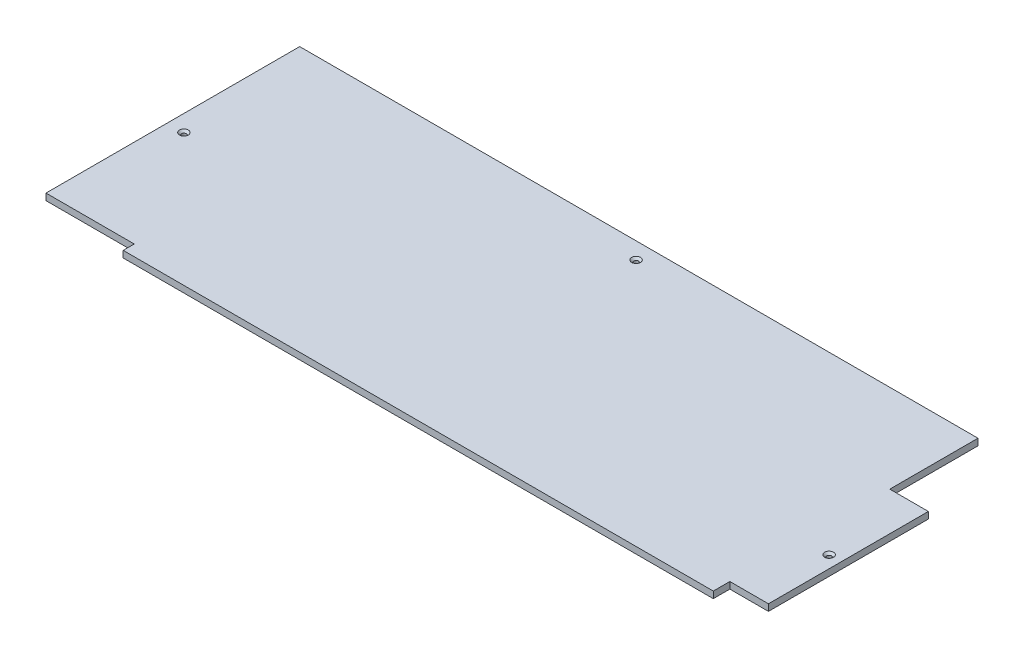
SolidWorks part; units mm, degrees
material "Balsa"
ref_plane "Front Plane" through (0, 0, 0) normal (0, 0, 1) x (1, 0, 0)
ref_plane "Top Plane" through (0, 0, 0) normal (0, 1, 0) x (1, 0, 0)
ref_plane "Right Plane" through (0, 0, 0) normal (1, 0, 0) x (0, 0, -1)
sketch "Sketch1" plane through (0, 0, 0) normal (0, 1, 0) x (1, 0, 0)
  line L1 (325, -120) -> (-325, -120)
  line L2 (325, -120) -> (325, 120)
  line L3 (325, 120) -> (-325, 120)
  line L4 (-325, -120) -> (-325, 120)
  line L5 (325, -120) -> (-325, 120) construction
  line L6 (325, 120) -> (-325, -120) construction
  point P0 (0, 0)
  dimension "D1" = 240
  dimension "D2" = 650
extrude "Boss-Extrude1" add sketch "Sketch1" along normal blind 6
sketch "Sketch2" plane through (0, 6, 0) normal (0, 1, 0) x (1, 0, 0)
  line L0 (-325, -120) -> (325, -120) construction
  line L1 (332.7558, 136.8148) -> (290, 136.8148)
  line L2 (332.7558, 136.8148) -> (332.7558, 40)
  line L3 (332.7558, 40) -> (290, 40)
  line L4 (290, 136.8148) -> (290, 40)
  line L5 (-337.1113, -127.8796) -> (-245, -127.8796)
  line L6 (-337.1113, -127.8796) -> (-337.1113, -110)
  line L7 (-337.1113, -110) -> (-245, -110)
  line L8 (-245, -127.8796) -> (-245, -110)
  line L9 (325, -120) -> (325, 120) construction
  line L10 (325, 120) -> (-325, 120) construction
  line L11 (-325, 120) -> (-325, -120) construction
  line L13 (337.9334, -130.2293) -> (290, -130.2293)
  line L14 (337.9334, -130.2293) -> (337.9334, -105)
  line L15 (337.9334, -105) -> (290, -105)
  line L16 (290, -130.2293) -> (290, -105)
  dimension "D1" = 10
  dimension "D2" = 35
  dimension "D3" = 80
  dimension "D4" = 80
  dimension "D5" = 35
  dimension "D6" = 15
extrude "Cut-Extrude1" cut sketch "Sketch2" against normal through all
hole_wizard "CSK for M4 Flat Head Machine Screw1" positions "Sketch4" profile "Sketch5" countersink size "M4" standard "ANSI Metric" end condition through all
sketch "Sketch4" plane through (0, 6, 0) normal (0, 1, 0) x (1, 0, 0)
  line L0 (-325, 120) -> (-325, -110) construction
  line L1 (290, 120) -> (-325, 120) construction
  line L2 (325, -105) -> (325, 40) construction
  point P0 (-310, 0)
  point P2 (-5, 105)
  point P9 (314, -39)
  dimension "D1" = 15
  dimension "D2" = 15
  dimension "D3" = 120
  dimension "D4" = 320
  dimension "D5" = 159
  dimension "D6" = 11
sketch "Sketch5" plane through (-310, 6, 0) normal (1, 0, 0) x (0, 0, 1)
  line L0 (0, 0) -> (0, 6)
  line L1 (0, 6) -> (2.1, 6)
  line L2 (2.1, 6) -> (2.1, 1.9)
  line L3 (2.1, 1.9) -> (4, 0)
  line L5 (4, 0) -> (0, 0)
  line L6 (-2.1, 1.9) -> (-4, 0) construction
  line L11 (0, -6.35) -> (0, 107.95) construction
  dimension "Thru Hole Dia." = 4.2
  dimension "Thru Hole Depth" = 6
  dimension "Near C'Sink Dia." = 8
  dimension "Near C'Sink Angle" = 90
